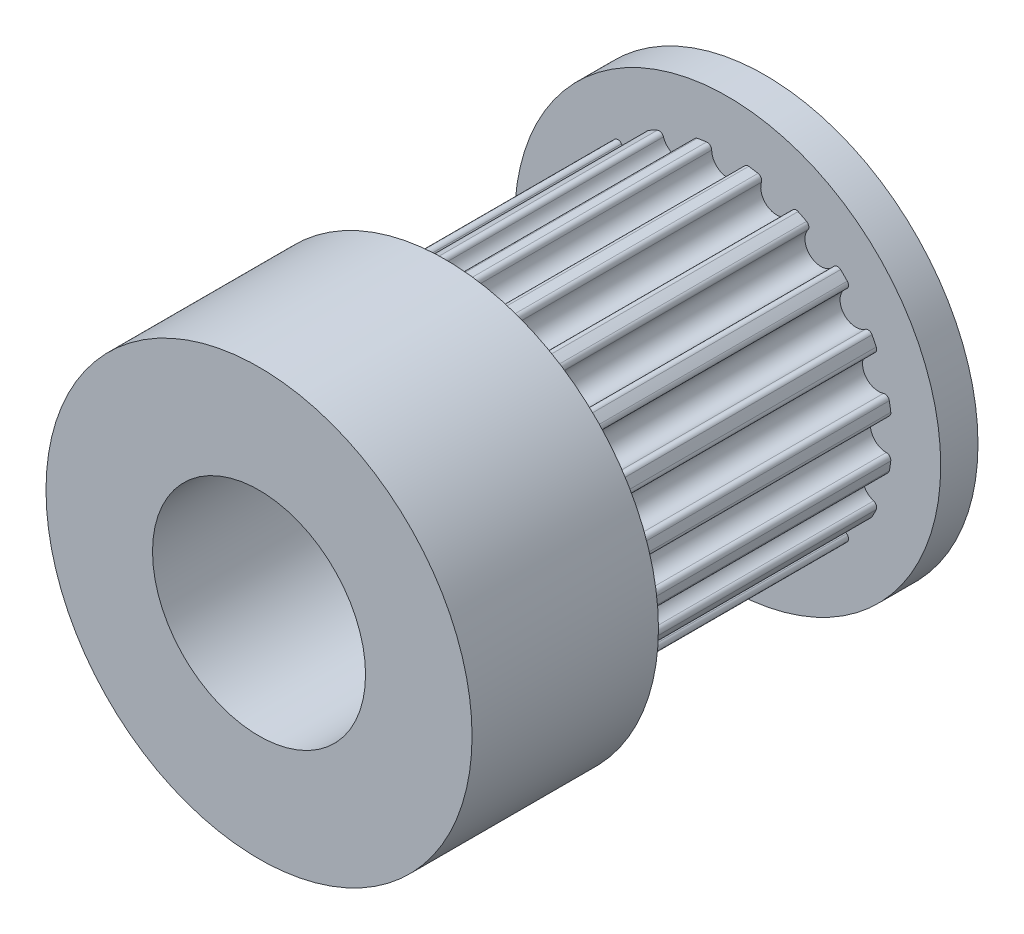
SolidWorks part; units mm, degrees
ref_plane "Front Plane" through (0, 0, 0) normal (0, 0, 1) x (1, 0, 0)
ref_plane "Top Plane" through (0, 0, 0) normal (0, 1, 0) x (1, 0, 0)
ref_plane "Right Plane" through (0, 0, 0) normal (1, 0, 0) x (0, 0, -1)
ref_axis "Axis1" through (0, 0, 55) along (0, 0, -1)
sketch "SketchRevolveGearBelt01" plane through (0, 0, 0) normal (1, 0, 0) x (0, 0, -1)
  line L0 (0, 0) -> (1, 0) construction
  line L1 (10.6, 0) -> (10.6, 6.1757)
  line L2 (10.6, 6.1757) -> (0, 6.1757)
  line L3 (0, 6.1757) -> (0, 0)
  line L4 (0, 0) -> (10.6, 0)
  dimension "GearBeltSide1" = 10.6
  dimension "GearBeltOutsideDiameter" = 6.1757
revolve "GearBelt01" add sketch "SketchRevolveGearBelt01" angle 360 about L0
sketch "SketchToothGearBelt01" plane through (0, 0, 0) normal (0, 0, 1) x (1, 0, 0)
  line L0 (-0.7912, 6.1248) -> (0, 8.7157)
  line L1 (0, 8.7157) -> (0.7912, 6.1248)
  arc A0 (0.7912, 6.1248) -> (0.6, 5.9567) centre (0.7695, 5.9567) ccw
  arc A1 (0.6, 5.9567) -> (-0.6, 5.9567) centre (0, 5.9567) cw
  arc A2 (-0.6, 5.9567) -> (-0.7912, 6.1248) centre (-0.7695, 5.9567) ccw
  dimension "GearBeltToothR1" = 0.339
  dimension "GearBeltToothR2" = 1.2
  dimension "GearBeltToothCapX1" = 0.7912
  dimension "GearBeltToothCapY1" = 2.5909
  dimension "GearBeltToothCapX2" = 0.7912
  dimension "GearBeltToothCapY2" = 2.5909
extrude "ToothExtrudeCutGearBelt01" cut sketch "SketchToothGearBelt01" against normal blind 11.5
pattern_circular "CirPattern2" count 20 over 360 about axis through (0, 0, 0) along (0, 0, 1) of "ToothExtrudeCutGearBelt01" reverse direction yes
sketch "Sketch6" plane through (0, 0, 0) normal (0, 0, 1) x (1, 0, 0)
  circle A0 centre (0, 0) radius 8
  dimension "D1" = 16
extrude "Boss-Extrude1" add sketch "Sketch6" along normal blind 7
sketch "Sketch7" plane through (0, 0, -10.6) normal (0, 0, -1) x (-1, 0, 0)
  circle A0 centre (0, 0) radius 8
extrude "Boss-Extrude2" add sketch "Sketch7" along normal blind 1.4
sketch "Sketch8" plane through (0, 0, 0) normal (0, 0, 1) x (1, 0, 0)
  circle A0 centre (0, 0) radius 4
extrude "Cut-Extrude2" cut sketch "Sketch8" against normal through all and the other way through all
